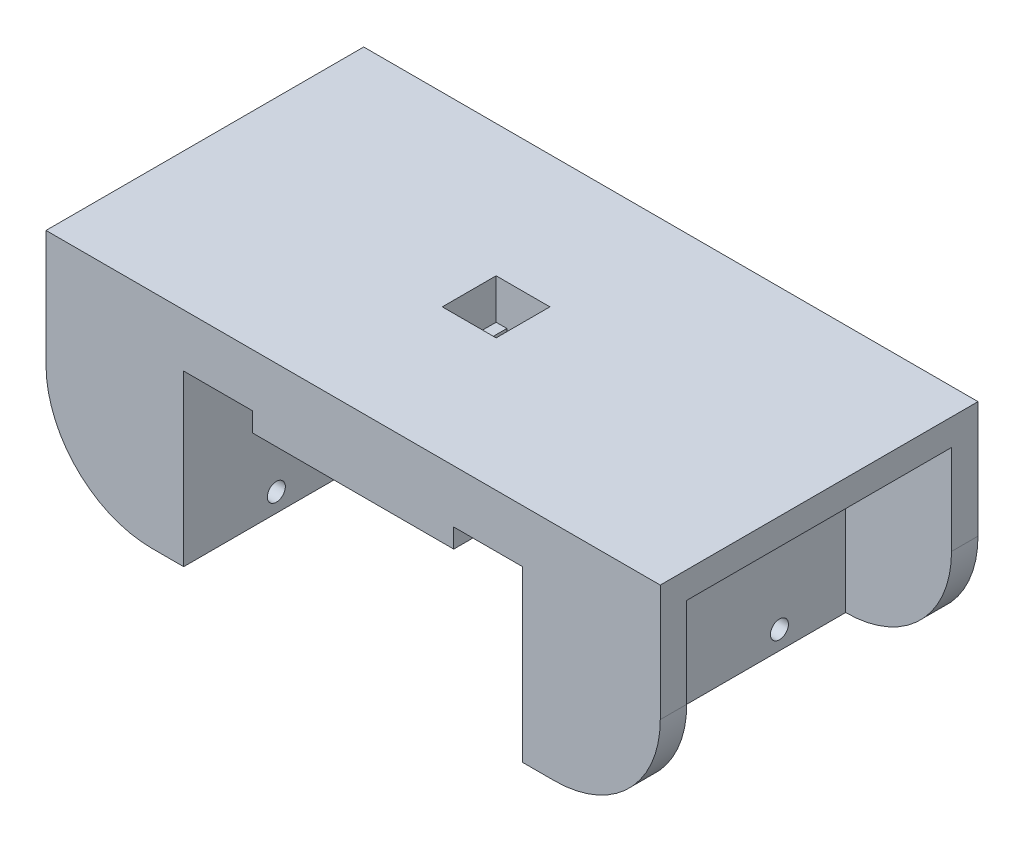
SolidWorks part; units mm, degrees
ref_plane "Front Plane" through (0, 0, 0) normal (0, 0, 1) x (1, 0, 0)
ref_plane "Top Plane" through (0, 0, 0) normal (0, 1, 0) x (1, 0, 0)
ref_plane "Right Plane" through (0, 0, 0) normal (1, 0, 0) x (0, 0, -1)
sketch "Sketch1" plane through (0, 0, 0) normal (0, 1, 0) x (1, 0, 0)
  line L1 (0, 0) -> (76, 0)
  line L2 (0, 0) -> (0, 60)
  line L3 (0, 60) -> (76, 60)
  line L4 (76, 0) -> (76, 60)
  dimension "D1" = 76
  dimension "D2" = 60
extrude "Boss-Extrude1" add sketch "Sketch1" along normal blind 10
sketch "Sketch2" plane through (0, 0, 0) normal (0, -1, 0) x (1, 0, 0)
  line L0 (0, 0) -> (76, 0) construction
  line L1 (0, -60) -> (6, -60)
  line L2 (0, -60) -> (0, 0)
  line L3 (0, 0) -> (6, 0)
  line L4 (6, -60) -> (6, 0)
  line L5 (76, -60) -> (0, -60) construction
  line L6 (76, 0) -> (70, 0)
  line L7 (76, 0) -> (76, -60)
  line L8 (76, -60) -> (70, -60)
  line L9 (70, 0) -> (70, -60)
  dimension "D1" = 6
extrude "Boss-Extrude2" add sketch "Sketch2" along normal blind 32
sketch "Sketch3" plane through (0, 0, 0) normal (-1, 0, 0) x (0, 0, 1)
  line L0 (0, -16) -> (-60, -16) construction
  line L1 (0, 10) -> (0, -32) construction
  line L2 (-60, 10) -> (-60, -32) construction
  line L4 (-60, -32) -> (-60, 0) construction
  line L6 (-17.5, -3.5) -> (-42.5, -3.5)
  line L7 (-17.5, -3.5) -> (-17.5, -28.5)
  line L8 (-17.5, -28.5) -> (-42.5, -28.5)
  line L9 (-42.5, -3.5) -> (-42.5, -28.5)
  line L10 (-17.5, -3.5) -> (-42.5, -28.5) construction
  line L11 (-17.5, -28.5) -> (-42.5, -3.5) construction
  point P7 (-30, -16)
  dimension "D1" = 25
hole_wizard "M3 Clearance Hole1" positions "Sketch4" profile "Sketch5" hole size "M3" standard "ANSI Metric" end condition through all
sketch "Sketch4" plane through (0, 0, 0) normal (-1, 0, 0) x (0, 0, 1)
  point P0 (-42.5, -28.5)
  point P3 (-42.5, -3.5)
  point P6 (-17.5, -3.5)
  point P9 (-17.5, -28.5)
sketch "Sketch5" plane through (0, -28.5, -42.5) normal (0, 1, 0) x (0, 0, 1)
  line L0 (0, 0) -> (0, 76)
  line L1 (0, 76) -> (1.7, 76)
  line L2 (1.7, 76) -> (1.7, 0)
  line L5 (1.7, 0) -> (0, 0)
  line L11 (0, -6.35) -> (0, 107.95) construction
  dimension "Thru Hole Dia." = 3.4
  dimension "Thru Hole Depth" = 76
ref_plane "Plane1" through (0, -16, 0) normal (0, -1, 0) x (-1, 0, 0)
ref_plane "Plane2" through (0, -4, 0) normal (0, -1, 0) x (-1, 0, 0)
ref_plane "Belt Plane" through (0, -3.624, 0) normal (0, -1, 0) x (-1, 0, 0)
sketch "Sketch7" plane through (0, 0, 0) normal (0, -1, 0) x (1, 0, 0)
  line L0 (70, -60) -> (6, -60) construction
  line L1 (19, -60) -> (57, -60)
  line L2 (19, -60) -> (19, 0)
  line L3 (19, 0) -> (57, 0)
  line L4 (57, -60) -> (57, 0)
  line L5 (6, 0) -> (70, 0) construction
  line L6 (6, -60) -> (6, 0) construction
  line L7 (70, 0) -> (70, -60) construction
  dimension "D1" = 13
  dimension "D2" = 13
extrude "Boss-Extrude3" add sketch "Sketch7" along normal up to surface (3.624 mm away) up to plane "Belt Plane"
sketch "Sketch8" plane through (0, -3.624, 0) normal (0, -1, 0) x (1, 0, 0)
  line L0 (35, -60) -> (35, 0) construction
  line L1 (19, -60) -> (57, -60) construction
  line L2 (57, 0) -> (19, 0) construction
  line L4 (6, -60) -> (6, 0) construction
  point P4 (0, 0)
  dimension "D1" = 29
hole_wizard "M4 Clearance Hole1" positions "Sketch9" profile "Sketch10" hole size "M4" standard "ANSI Metric" end condition through all
sketch "Sketch9" plane through (0, -3.624, 0) normal (0, -1, 0) x (-1, 0, 0)
  line L0 (-35, 60) -> (-35, 0) construction
  point P0 (-35, 30)
  point P5 (0, 0)
sketch "Sketch10" plane through (35, -3.624, -30) normal (1, 0, 0) x (0, 0, -1)
  line L0 (0, 0) -> (0, 13.624)
  line L1 (0, 13.624) -> (2.25, 13.624)
  line L2 (2.25, 13.624) -> (2.25, 0)
  line L5 (2.25, 0) -> (0, 0)
  line L11 (0, -6.35) -> (0, 107.95) construction
  dimension "Thru Hole Dia." = 4.5
  dimension "Thru Hole Depth" = 13.624
sketch "Sketch11" plane through (0, 10, 0) normal (0, 1, 0) x (1, 0, 0)
  line L1 (29.92, 24.92) -> (40.08, 24.92)
  line L2 (29.92, 24.92) -> (29.92, 35.08)
  line L3 (29.92, 35.08) -> (40.08, 35.08)
  line L4 (40.08, 24.92) -> (40.08, 35.08)
  line L5 (29.92, 24.92) -> (40.08, 35.08) construction
  line L6 (29.92, 35.08) -> (40.08, 24.92) construction
  point P0 (35, 30)
  dimension "D1" = 10.16
extrude "Cut-Extrude1" cut sketch "Sketch11" against normal offset from surface (9.124 mm away) 4.5 up to face at (35, -3.624, -32.25)
sketch "Sketch12" plane through (0, 0.876, 0) normal (0, 1, 0) x (1, 0, 0)
  line L0 (40.08, 35.08) -> (29.92, 35.08) construction
  line L1 (29.92, 24.92) -> (31.952, 24.92)
  line L2 (29.92, 24.92) -> (29.92, 35.08)
  line L3 (29.92, 35.08) -> (31.952, 35.08)
  line L4 (31.952, 24.92) -> (31.952, 35.08)
  line L6 (40.08, 24.92) -> (38.048, 24.92)
  line L7 (40.08, 24.92) -> (40.08, 35.08)
  line L8 (40.08, 35.08) -> (38.048, 35.08)
  line L9 (38.048, 24.92) -> (38.048, 35.08)
  dimension "D1" = 6.096
extrude "Boss-Extrude4" add sketch "Sketch12" along normal blind 1.524
ref_plane "Plane4" through (38, 0, 0) normal (-1, 0, 0) x (0, 0, 1)
sketch "Sketch13" plane through (0, 0, 0) normal (-1, 0, 0) x (0, 0, 1)
  line L0 (-60, 10) -> (-60, -32) construction
  line L1 (0, 10) -> (-60, 10)
  line L2 (0, 10) -> (0, 5)
  line L3 (0, 5) -> (-60, 5)
  line L4 (-60, 10) -> (-60, 5)
  dimension "D1" = 5
extrude "Boss-Extrude5" add sketch "Sketch13" along normal blind 20
sketch "Sketch14" plane through (0, -32, 0) normal (0, -1, 0) x (1, 0, 0)
  line L1 (0, -60) -> (-20, -60)
  line L2 (0, -60) -> (0, -55)
  line L3 (0, -55) -> (-20, -55)
  line L4 (-20, -60) -> (-20, -55)
  line L5 (0, 0) -> (-20, 0)
  line L6 (0, 0) -> (0, -5)
  line L7 (0, -5) -> (-20, -5)
  line L8 (-20, 0) -> (-20, -5)
  line L9 (-20, -60) -> (-20, 0) construction
  dimension "D1" = 5
extrude "Boss-Extrude6" add sketch "Sketch14" against normal up to next
fillet "Fillet1" radius 20 2 edges at (-20, -32, -2.5) (-20, -32, -57.5)
mirror "Mirror1" about plane through (38, 0, 0) normal (-1, 0, 0) of "Fillet1", "Boss-Extrude5", "Boss-Extrude6"
